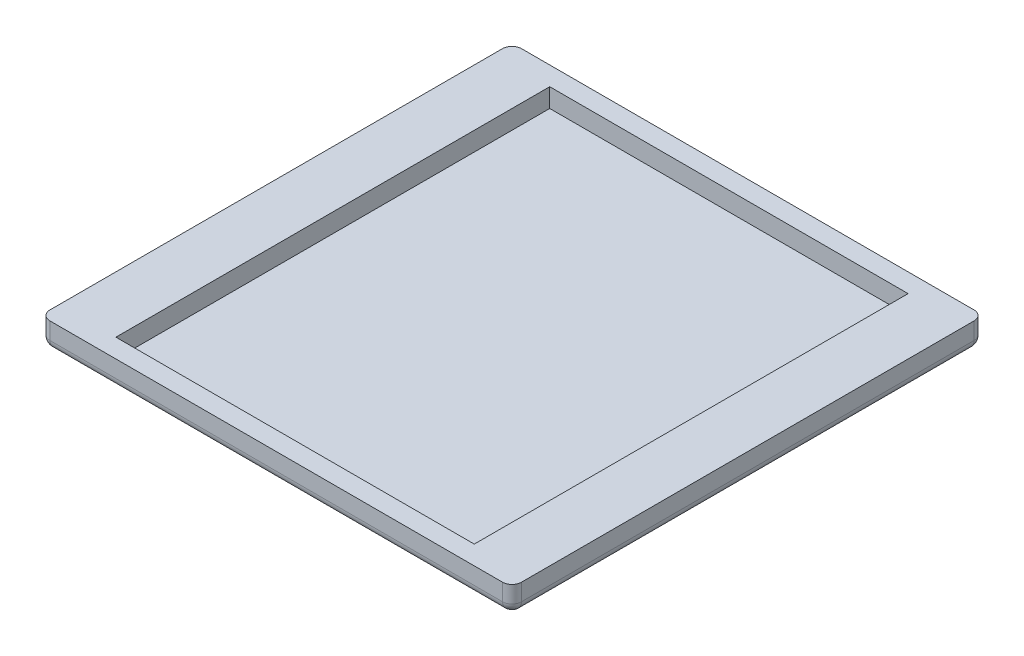
SolidWorks part; units mm, degrees
ref_plane "Front Plane" through (0, 0, 0) normal (0, 0, 1) x (1, 0, 0)
ref_plane "Top Plane" through (0, 0, 0) normal (0, 1, 0) x (1, 0, 0)
ref_plane "Right Plane" through (0, 0, 0) normal (1, 0, 0) x (0, 0, -1)
sketch "Sketch1" plane through (0, 0, 0) normal (0, 1, 0) x (1, 0, 0)
  line L1 (-125, -125) -> (125, -125)
  line L2 (-125, -125) -> (-125, 125)
  line L3 (-125, 125) -> (125, 125)
  line L4 (125, -125) -> (125, 125)
  line L5 (-125, -125) -> (125, 125) construction
  line L6 (-125, 125) -> (125, -125) construction
  point P0 (0, 0)
  dimension "D1" = 250
  dimension "D2" = 250
extrude "Base" add sketch "Sketch1" along normal blind 14
sketch "Sketch3" plane through (0, 14, 0) normal (0, 1, 0) x (1, 0, 0)
  line L0 (-95, 115) -> (-95, -115)
  line L1 (-95, 115) -> (95, 115)
  line L3 (-95, -115) -> (95, -115)
  line L5 (95, 115) -> (95, -115)
  line L6 (125, 125) -> (-125, 125) construction
  line L7 (-125, 125) -> (-125, -125) construction
  line L8 (125, -125) -> (125, 125) construction
  line L12 (-125, -125) -> (125, -125) construction
  point P0 (0, 0)
  dimension "D3" = 10
  dimension "D5" = 10
  dimension "D1" = 30
  dimension "D2" = 30
extrude "Cut-Extrude1" cut sketch "Sketch3" against normal blind 10
fillet "Fillet1" radius 5 4 edges at (0, 0, -125) (-125, 0, 0) (0, 0, 125) (125, 0, 0)
fillet "Fillet2" radius 5 8 edges at (-123.5355, 1.4645, 123.5355) (-125, 9.5, 125) (123.5355, 1.4645, -123.5355) (123.5355, 1.4645, 123.5355) (-123.5355, 1.4645, -123.5355) (125, 9.5, -125) (125, 9.5, 125) (-125, 9.5, -125)
equation "\"Width\"= 250"
equation "\"D1@Sketch1\"=\"Width\""
equation "\"Depth\"= 250"
equation "\"D2@Sketch1\"=\"Depth\""
equation "\"height\"= 14"
equation "\"D1@Base\"=\"height\""
equation "\"r1\"=5"
equation "\"D1@Fillet2\"=\"r1\""
equation "\"D1@Fillet1\"=\"r1\""
equation "\"cut1\"= 10"
equation "\"D1@Cut-Extrude1\"=\"cut1\""
equation "\"border1\"=10"
equation "\"D3@Sketch3\"=\"border1\""
equation "\"D5@Sketch3\"=\"border1\""
equation "\"rail_mount_width\"=130"
equation "\"border2\"= 30"
equation "\"D1@Sketch3\"=\"border2\""
equation "\"D2@Sketch3\"=\"border2\""
